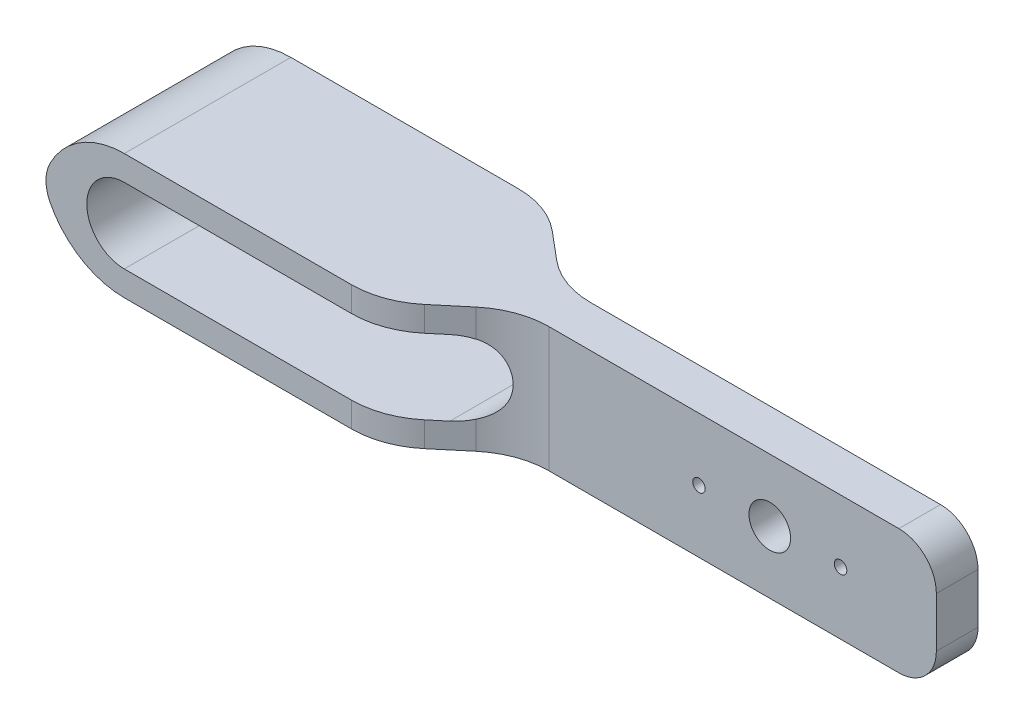
SolidWorks part; units mm, degrees
ref_plane "Front Plane" through (0, 0, 0) normal (0, 0, 1) x (1, 0, 0)
ref_plane "Top Plane" through (0, 0, 0) normal (0, 1, 0) x (1, 0, 0)
ref_plane "Right Plane" through (0, 0, 0) normal (1, 0, 0) x (0, 0, -1)
sketch "Esboço1" plane through (0, 0, 0) normal (0, 0, 1) x (1, 0, 0)
  line L13 (-17.5, -6) -> (22.5, -6)
  line L14 (-17.5, -6) -> (-17.5, 9)
  line L15 (-17.5, 9) -> (22.5, 9)
  line L16 (22.5, -6) -> (22.5, 9)
  dimension "D3" = 15
  dimension "D4" = 40
extrude "Ressalto-extrusão1" add sketch "Esboço1" against normal blind 3
sketch "Esboço2" plane through (0, 0, 0) normal (0, 0, 1) x (1, 0, 0)
  line L0 (-17.5, 9) -> (22.5, -6) construction
  line L7 (-17.5, -6) -> (22.5, 9) construction
  circle A0 centre (2.5, 1.5) radius 2.5
  circle A4 centre (-6, 1.5) radius 0.75
  dimension "D1" = 1.5
  dimension "D3" = 5
  dimension "D2" = 8.5
sketch "Esboço3" plane through (0, 0, 0) normal (0, 0, 1) x (1, 0, 0)
  line L1 (-17.5, -6) -> (22.5, -6)
  line L2 (-17.5, -6) -> (-17.5, 9)
  line L3 (-17.5, 9) -> (22.5, 9)
  line L4 (22.5, -6) -> (22.5, 9)
extrude "Ressalto-extrusão2" add sketch "Esboço3" along normal blind 2
extrude "Corte-extrusão1" cut sketch "Esboço2" along normal up to surface and the other way up to surface up to face at (2.5, 1.5, 2) other way up to face at (2.5, 1.5, -3)
sketch "Esboço4" plane through (0, 9, 0) normal (0, 1, 0) x (1, 0, 0)
  line L0 (22.5, -2) -> (-17.5, -2) construction
  line L1 (6.2, -34.5) -> (-6.2, -34.5)
  line L2 (6.2, -34.5) -> (6.2, -11.5)
  line L3 (6.2, -11.5) -> (-6.2, -11.5)
  line L4 (-6.2, -34.5) -> (-6.2, -11.5)
  line L5 (-17.5, 3) -> (22.5, 3) construction
  line L6 (17.5, -2) -> (-12.5, -2)
  line L7 (17.5, -2) -> (17.5, -42)
  line L8 (17.5, -42) -> (-12.5, -42)
  line L9 (-12.5, -2) -> (-12.5, -42)
  line L10 (-12.5, -2) -> (17.5, -2)
  line L11 (-12.5, -2) -> (-12.5, 3)
  line L12 (-12.5, 3) -> (17.5, 3)
  line L13 (17.5, -2) -> (17.5, 3)
  circle A0 centre (0, -9.75) radius 1.25
  circle A1 centre (0, -36.25) radius 1.25
  point P6 (0, -34.5)
  point P13 (2.5, -2)
  point P14 (2.5, -42)
  line M5 (-17.5, -2) -> (22.5, -2)
  line M7 (22.5, 3) -> (-17.5, 3)
  dimension "D6" = 7.75
  dimension "D7" = 2.5
  dimension "D8" = 26.5
  dimension "D1" = 9.5
  dimension "D2" = 23
  dimension "D3" = 12.4
  dimension "D4" = 30
  dimension "D5" = 40
extrude "Ressalto-extrusão3" [suppressed] add sketch "Esboço4" against normal blind 3 contours L13 L11 M5 M7 | L9 L8 L7 L1 L4 L3 L2 M5
fillet "Filete2" [suppressed] radius 5
fillet "Filete3" [suppressed] radius 10
sketch "Esboço5" plane through (-17.5, 0, 0) normal (-1, 0, 0) x (0, 0, 1)
  line L0 (-3, 9) -> (2, 9) construction
  line L1 (-10.5, -6) -> (9.5, -6)
  line L2 (-10.5, -6) -> (-10.5, 9)
  line L3 (-10.5, 9) -> (9.5, 9)
  line L4 (9.5, -6) -> (9.5, 9)
  line L5 (-3, -6) -> (2, -6) construction
  point P13 (-0.5, -6)
  point P14 (-0.5, -6)
  dimension "D1" = 20
extrude "Ressalto-extrusão4" add sketch "Esboço5" along normal blind 60
chamfer "Chanfro1" distance 16 angle 50 2 edges at (-17.5, 1.5, -10.5) (-17.5, 1.5, 9.5)
fillet "Filete4" radius 10 6 edges at (-77.5, 9, -0.5) (-77.5, -6, -0.5) (-36.5681, 1.5, -10.5) (-27.6299, 1.5, -3) (-36.5681, 1.5, 9.5) (-27.6299, 1.5, 2)
sketch "Esboço6" plane through (0, 0, 9.5) normal (0, 0, 1) x (1, 0, 0)
  line L0 (-43.2078, 6) -> (-67.5, 6)
  line L1 (-67.5, -3) -> (-43.2078, -3)
  line L2 (-43.2078, -3) -> (-43.2078, 6) construction
  line L3 (-40.2078, 9) -> (-67.5, 9)
  line L4 (-67.5, -6) -> (-40.2078, -6)
  line L5 (-40.2078, -6) -> (-40.2078, 9)
  line L6 (-40.2078, 9) -> (-67.5, 9) construction
  line L7 (-67.5, -6) -> (-40.2078, -6) construction
  line L9 (-43.2078, 6) -> (-27.6299, 6)
  line L11 (-43.2078, -3) -> (-27.6299, -3)
  line L12 (-27.6299, -3) -> (-27.6299, 6)
  line L13 (-27.6299, 9) -> (-27.6299, -6) construction
  line L16 (-40.2078, -6) -> (-40.2078, 9) construction
  line L17 (-40.2078, -6) -> (-40.2078, 9)
  arc A0 (-67.5, 6) -> (-74.0383, 1.5) centre (-67.5, -1) ccw
  arc A1 (-74.0383, 1.5) -> (-67.5, -3) centre (-67.5, 4) ccw
  arc A2 (-67.5, 9) -> (-77.1825, 1.5) centre (-67.5, -1) ccw
  arc A3 (-77.1825, 1.5) -> (-67.5, -6) centre (-67.5, 4) ccw
  arc A4 (-67.5, 9) -> (-77.1825, 1.5) centre (-67.5, -1) ccw construction
  arc A5 (-77.1825, 1.5) -> (-67.5, -6) centre (-67.5, 4) ccw construction
  dimension "D1" = 0
  dimension "D2" = 3
extrude "Corte-extrusão2" cut sketch "Esboço6" against normal through all
fillet "Filete5" radius 4.5 4 edges at (-27.6299, -3, -0.5) (-27.6299, 6, -0.5) (22.5, -6, -0.5) (22.5, 9, -0.5)
pattern_circular "CirPattern1" count 2 over 360 about axis through (2.5, 1.5, 0) along (0, 0, 1) of "Corte-extrusão1"
fillet "Fillet1" radius 4.5 2 edges at (-77.1825, 1.5, -0.5) (-74.0383, 1.5, -0.5)
move or copy body "Body-Move/Copy1" [suppressed]
move or copy body "Body-Move/Copy2" bodies to move or copy 106
